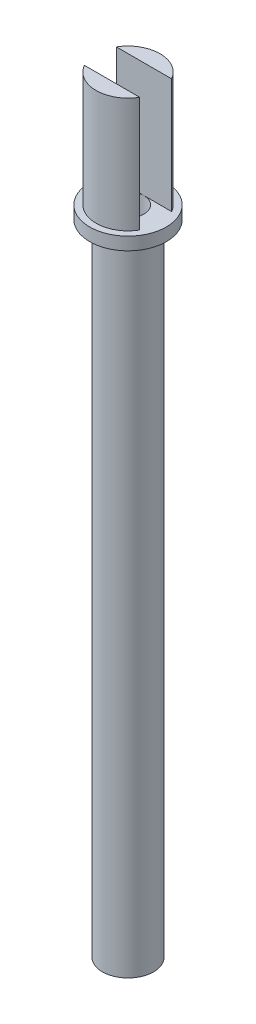
SolidWorks part; units mm, degrees
ref_plane "Front Plane" through (0, 0, 0) normal (0, 0, 1) x (1, 0, 0)
ref_plane "Top Plane" through (0, 0, 0) normal (0, 1, 0) x (1, 0, 0)
ref_plane "Right Plane" through (0, 0, 0) normal (1, 0, 0) x (0, 0, -1)
sketch "Sketch3" plane through (0, 0, 0) normal (0, 1, 0) x (1, 0, 0)
  circle A0 centre (0, 0) radius 4
  dimension "D1" = 8
extrude "Boss-Extrude2" add sketch "Sketch3" along normal blind 100
sketch "Sketch4" plane through (0, 100, 0) normal (0, 1, 0) x (1, 0, 0)
  circle A0 centre (0, 0) radius 5
  dimension "D1" = 10
extrude "Boss-Extrude3" add sketch "Sketch4" along normal blind 20
sketch "Sketch5" plane through (0, 120, 0) normal (0, 1, 0) x (1, 0, 0)
  circle A0 centre (0, 0) radius 1.9188
extrude "Cut-Extrude1" cut sketch "Sketch5" against normal blind 15
sketch "Sketch6" plane through (0, 120, 0) normal (0, 1, 0) x (1, 0, 0)
  line L1 (-7.3374, 2.5) -> (7.3374, 2.5)
  line L2 (-7.3374, 2.5) -> (-7.3374, -2.5)
  line L3 (-7.3374, -2.5) -> (7.3374, -2.5)
  line L4 (7.3374, 2.5) -> (7.3374, -2.5)
  line L5 (-7.3374, 2.5) -> (7.3374, -2.5) construction
  line L6 (-7.3374, -2.5) -> (7.3374, 2.5) construction
  point P0 (0, 0)
  dimension "D1" = 5
extrude "Cut-Extrude2" cut sketch "Sketch6" against normal offset from surface (18 mm away) 2 up to face at (0, 100, 4)
sketch "Sketch7" plane through (0, 102, 0) normal (0, 1, 0) x (1, 0, 0)
  circle A0 centre (0, 0) radius 2.5
  dimension "D1" = 5
extrude "Cut-Extrude3" cut sketch "Sketch7" against normal blind 10
sketch "Sketch8" plane through (0, 100, 0) normal (0, -1, 0) x (1, 0, 0)
  circle A0 centre (0, 0) radius 5
  circle A1 centre (0, 0) radius 6
  dimension "D1" = 1
extrude "Boss-Extrude4" add sketch "Sketch8" against normal up to surface (2 mm away) up to face at (2.9575, 102, 0)
